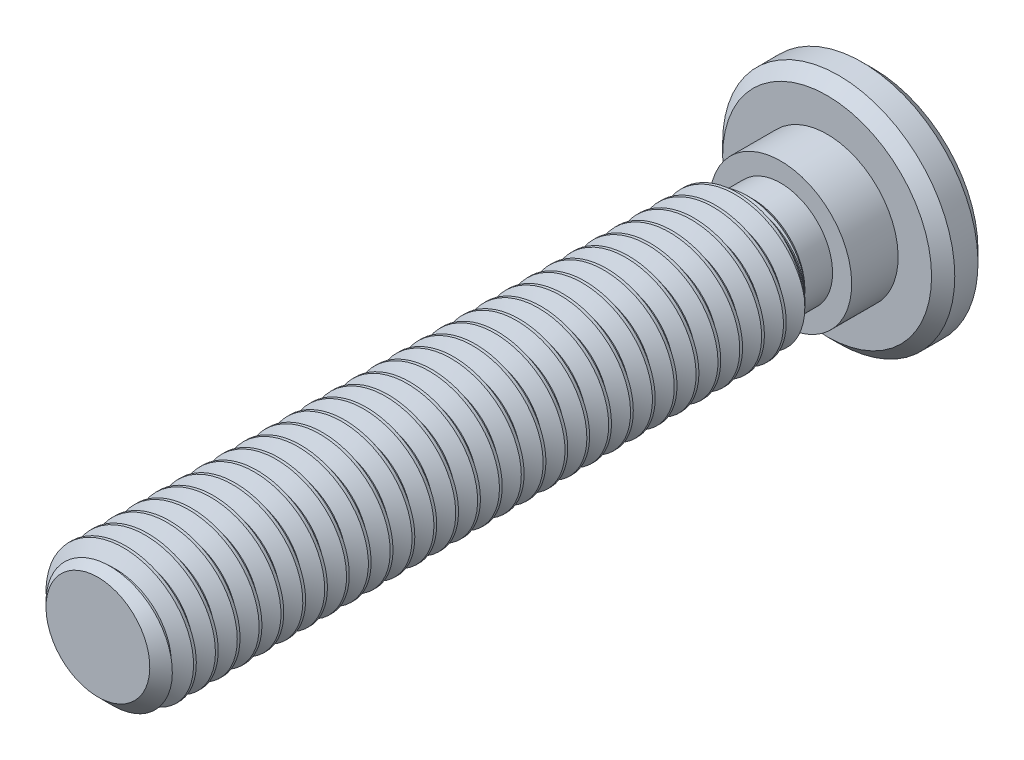
SolidWorks part; units mm, degrees
other "DetailItem1"
ref_plane "Front Plane" through (0, 0, 0) normal (0, 0, 1) x (1, 0, 0)
ref_plane "Top Plane" through (0, 0, 0) normal (0, 1, 0) x (1, 0, 0)
ref_plane "Right Plane" through (0, 0, 0) normal (1, 0, 0) x (0, 0, -1)
sketch "Sketch1" plane through (0, 0, 0) normal (1, 0, 0) x (0, 0, -1)
  line L0 (0, 0) -> (-26.7, 0) construction
  line L1 (0, 0) -> (1.7, 0) construction
  line L2 (1.7, 4.25) -> (1.7, -4.25) construction
  line L3 (-26.7, 2.5) -> (-26.7, -2.5) construction
  line L4 (0, 2.6) -> (0, -2.6) construction
  line L5 (-26.7, 2.5) -> (-25.9, 2.5) construction
  line L6 (1.7, 1.5) -> (1.7, -1.5) construction
  line L7 (0, 2.6) -> (-1.7, 2.6) construction
  line L8 (-1.7, 2.6) -> (-1.7, 1.9) construction
  line L9 (-1.7, 1.9) -> (-2.716, 1.9) construction
  line L10 (-2.716, 1.9) -> (-3.316, 2.5) construction
  point P2 (-23.9, -2.5)
  point P4 (-1.7, 0)
  point P8 (1.7, 0)
  point P11 (-26.7, 0)
  point P14 (0, 0)
  point P19 (1.7, 0)
  dimension "Thread Diameter" = 5
  dimension "Head Diameter" = 8.5
  dimension "Head Height" = 1.7
  dimension "Shoulder Diameter" = 5.2
  dimension "Shoulder Length" = 1.7
  dimension "Thread Pitch" = 0.8
  dimension "Drive Size" = 3
  dimension "D1" = 2.8
  dimension "D2" = 45
  dimension "Undercut Length" = 1.016
  dimension "D3" = 3.8
  dimension "Length" = 25
sketch "Sketch13" plane through (0, 0, 0) normal (1, 0, 0) x (0, 0, -1)
  line L0 (1.7, 4.25) -> (0, 4.25)
  line L1 (0, 4.25) -> (0, 2.6)
  line L3 (-26.7, 2.5) -> (-26.7, 0)
  line L4 (-26.7, 0) -> (1.7, 0)
  line L5 (1.7, 0) -> (1.7, 4.25)
  line L6 (-2.716, 1.9) -> (-3.316, 2.5) construction
  line L7 (-1.7, 1.9) -> (-2.716, 1.9) construction
  line L8 (-1.7, 2.6) -> (-1.7, 1.9) construction
  line L9 (0, 2.6) -> (-1.7, 2.6) construction
  line L10 (-2.716, 1.9) -> (-3.316, 2.5)
  line L11 (-1.7, 1.9) -> (-2.716, 1.9)
  line L12 (-1.7, 2.6) -> (-1.7, 1.9)
  line L13 (0, 2.6) -> (-1.7, 2.6)
  line L14 (-3.316, 2.5) -> (-26.7, 2.5)
revolve "Revolve1" add sketch "Sketch13" angle 360 about L4
sketch "Sketch2" plane through (0, 0, 26.7) normal (0, 0, 1) x (1, 0, 0)
  circle A2 centre (0, 0) radius 2.5
chamfer "Chamfer2" distance 0.6 angle 45 1 edges at (0, -2.5, 26.7)
sketch "Sketch3" plane through (0, 0, 0) normal (1, 0, 0) x (0, 0, -1)
  line L0 (-26.65, 2.5866) -> (-27.45, 2.5866) construction
  line L1 (-27.45, 2.5866) -> (-27.05, 1.8938) construction
  line L2 (-27.05, 1.8938) -> (-26.65, 2.5866) construction
  line L4 (-26.7, 2.5) -> (-27.4, 2.5) construction
  line L5 (-27.05, 2.5866) -> (-27.05, 2.5) construction
  line L6 (-27.425, 2.5433) -> (-26.675, 2.5433)
  line L7 (-26.675, 2.5433) -> (-27.425, 2.5433) construction
  line L8 (-27, 1.9804) -> (-27.1, 1.9804) construction
  line L9 (-27.05, 1.9804) -> (-27.05, 1.8938) construction
  line L10 (-26.675, 2.5433) -> (-27, 1.9804)
  line L11 (-27, 1.9804) -> (-27.1, 1.9804)
  line L12 (-27.1, 1.9804) -> (-27.425, 2.5433)
  point P16 (-27.05, 2.5433)
  dimension "D1" = 0.8
  dimension "D2" = 0.1
sketch "Sketch7" plane through (0, 0, -1.7) normal (0, 0, -1) x (-1, 0, 0)
  line L1 (0, 1.7321) -> (-1.5, 0.866)
  line L2 (-1.5, 0.866) -> (-1.5, -0.866)
  line L3 (-1.5, -0.866) -> (0, -1.7321)
  line L4 (0, -1.7321) -> (1.5, -0.866)
  line L5 (1.5, -0.866) -> (1.5, 0.866)
  line L6 (1.5, 0.866) -> (0, 1.7321)
  circle A0 centre (0, 0) radius 1.5 construction
extrude "Cut-Extrude1" cut sketch "Sketch7" against normal blind 2.25
chamfer "Chamfer1" distance 0.425 angle 45 2 edges at (0, -4.25, -1.7) (0, -4.25, 0)
sketch "Sketch8" plane through (0, 0, -1.7) normal (0, 0, -1) x (-1, 0, 0)
  circle A0 centre (0, 0) radius 1.7321
extrude "Cut-Extrude2" cut sketch "Sketch8" against normal through all draft 45
curve "Helix/Spiral1" pitch 0.8 height 24.9 turns 31.125 parameters "pitch"=0.8
sweep "Cut-Sweep1" cut profiles "Sketch3" path "Helix/Spiral1"
equation "\"D3@Helix/Spiral1\"=\"Length@Sketch1\"-.1"
equation "\"D1@Cut-Extrude1\" = \"Drive Size@Sketch1\" * .75"
equation "\"D1@Chamfer1\" = \"Head Diameter@Sketch1\" * .05"
equation "\"D1@Chamfer2\"=\"pitch@Helix/Spiral1\"*.750"
equation "\"D1@Sketch3\" = \"Thread Pitch@Sketch1\""
equation "\"D2@Sketch3\"=\"D1@Sketch3\"/ 1/8"
equation "\"pitch@Helix/Spiral1\" = \"Thread Pitch@Sketch1\""
equation "\"D1@Sketch1\" = \"Thread Pitch@Sketch1\" * 3.5"
equation "\"D3@Sketch1\"=\"Thread Diameter@Sketch1\"-(\"Thread Pitch@Sketch1\"*1.5)"
